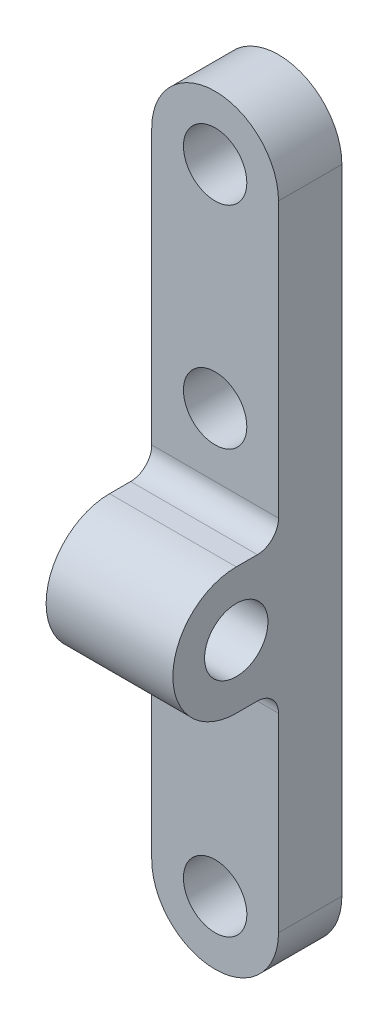
SolidWorks part; units mm, degrees
ref_plane "正面" through (0, 0, 0) normal (0, 0, 1) x (1, 0, 0)
ref_plane "平面" through (0, 0, 0) normal (0, 1, 0) x (1, 0, 0)
ref_plane "右側面" through (0, 0, 0) normal (1, 0, 0) x (0, 0, -1)
sketch "ｽｹｯﾁ1" plane through (0, 0, 0) normal (0, 0, 1) x (1, 0, 0)
  line L0 (0, 0) -> (0, -30) construction
  line L1 (-3, 0) -> (-3, -30)
  line L2 (3, 0) -> (3, -30)
  line L3 (0, -15) -> (-3, -15) construction
  circle A0 centre (0, 0) radius 1.5
  arc A1 (3, 0) -> (-3, 0) centre (0, 0) ccw
  circle A2 centre (0, -30) radius 1.5
  arc A3 (3, -30) -> (-3, -30) centre (0, -30) cw
  arc A4 (0, -3) -> (3, 0) centre (0, 0) ccw construction
  arc A5 (-3, 0) -> (0, -3) centre (0, 0) ccw construction
  arc A6 (-3, -30) -> (0, -27) centre (0, -30) cw construction
  arc A7 (0, -27) -> (3, -30) centre (0, -30) cw construction
  dimension "D1" = 3
  dimension "D2" = 6
  dimension "D3" = 6
  dimension "D4" = 30
extrude "ﾎﾞｽ - 押し出し1" add sketch "ｽｹｯﾁ1" along normal blind 3
sketch "ｽｹｯﾁ2" plane through (3, 0, 0) normal (1, 0, 0) x (0, 0, -1)
  line L1 (0, -14) -> (-5, -14)
  line L3 (-5, -20) -> (0, -20)
  line L4 (0, -20) -> (0, -14)
  line L5 (-3, -30) -> (0, -30) construction
  line L6 (0, -30) -> (0, 0) construction
  line L7 (-3, -30) -> (-3, 0) construction
  circle A0 centre (-5, -17) radius 1.5
  arc A1 (-5, -20) -> (-5, -14) centre (-5, -17) cw
  point P9 (0, 0)
  point P10 (0, 0)
  point P11 (-4.4191, -19.1861)
  point P12 (-4.1911, -21.6949)
  point P14 (0, 0)
  point P15 (0, 0)
  point P16 (0, -23)
  dimension "D1" = 3
  dimension "D2" = 3
  dimension "D3" = 13
  dimension "D4" = 2
extrude "ﾎﾞｽ - 押し出し4" add sketch "ｽｹｯﾁ2" against normal up to surface (6 mm away) up to face at (-3, -15, 1.5)
fillet "ﾌｨﾚｯﾄ1" radius 1 2 edges at (0, -20, 3) (0, -14, 3)
sketch "ｽｹｯﾁ3" plane through (0, 0, 0) normal (0, 0, -1) x (-1, 0, 0)
  line L0 (0, 0) -> (0, -10) construction
  circle A0 centre (0, -10) radius 1.5
  point P3 (0, 0)
  point P4 (0.0937, -10.0185)
  point P5 (0, 0)
  point P6 (0, 0)
  point P7 (-2.5326, -9.3538)
  point P8 (0, 0)
  dimension "D1" = 3
  dimension "D2" = 10
extrude "ｶｯﾄ - 押し出し1" cut sketch "ｽｹｯﾁ3" against normal blind 10
